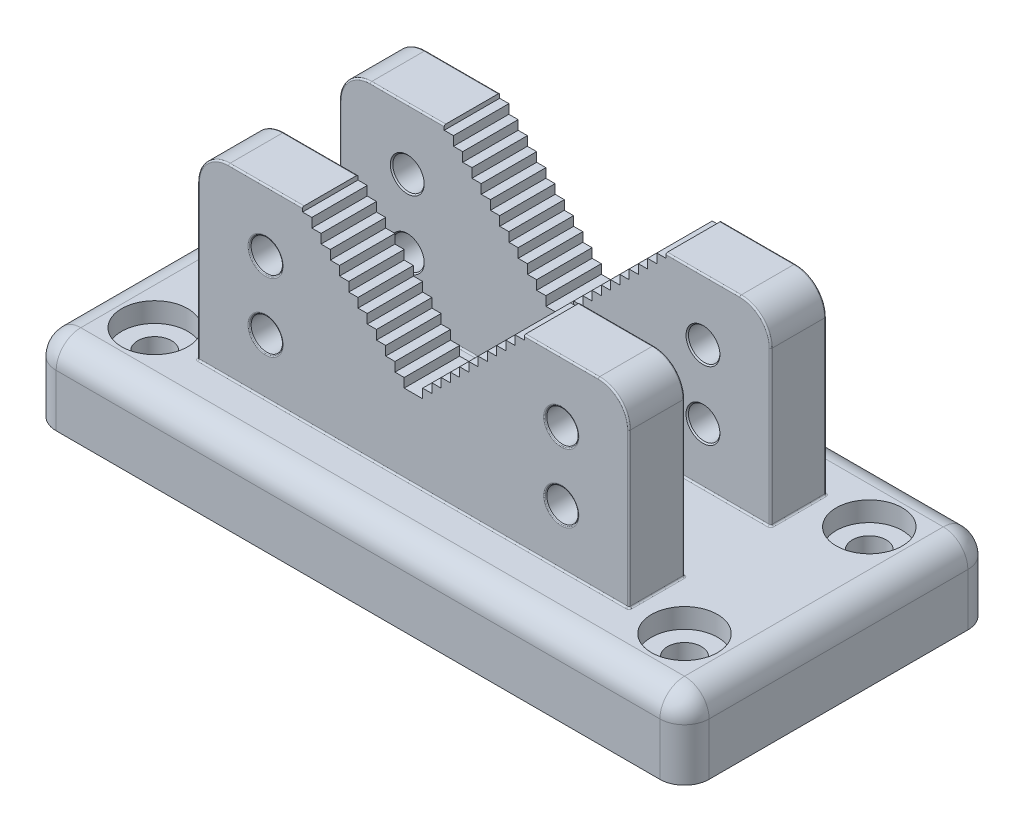
SolidWorks part; units mm, degrees
ref_plane "Front Plane" through (0, 0, 0) normal (0, 0, 1) x (1, 0, 0)
ref_plane "Top Plane" through (0, 0, 0) normal (0, 1, 0) x (1, 0, 0)
ref_plane "Right Plane" through (0, 0, 0) normal (1, 0, 0) x (0, 0, -1)
sketch "Sketch1" plane through (0, 0, 0) normal (0, 0, 1) x (1, 0, 0)
  line L0 (0, 0) -> (0, 51) construction
  line L1 (-106, 25) -> (106, 25)
  line L2 (-106, 25) -> (-106, 0)
  line L3 (-106, 0) -> (106, 0)
  line L4 (106, 25) -> (106, 0)
  line L5 (70, 25) -> (70, 75)
  line L6 (-70, 25) -> (-70, 75)
  line L7 (60, 85) -> (34, 85)
  line L8 (-60, 85) -> (-34, 85)
  line L9 (34, 85) -> (7.0711, 58.0711)
  line L10 (-34, 85) -> (-7.0711, 58.0711)
  arc A0 (70, 75) -> (60, 85) centre (60, 75) ccw
  arc A1 (-7.0711, 58.0711) -> (7.0711, 58.0711) centre (0, 65.1421) ccw
  arc A2 (-70, 75) -> (-60, 85) centre (-60, 75) cw
  circle A3 centre (48, 65.1421) radius 5
  circle A4 centre (-48, 65.1421) radius 5
  circle A5 centre (48, 43) radius 5
  circle A6 centre (-48, 43) radius 5
  point P16 (70, 85)
  point P22 (-70, 85)
  dimension "D7" = 10
  dimension "D8" = 10
  dimension "D1" = 25
  dimension "D2" = 212
  dimension "D3" = 51
  dimension "D4" = 60
  dimension "D5" = 90
  dimension "D6" = 36
  dimension "D9" = 48
  dimension "D10" = 18
extrude "Boss-Extrude1" add sketch "Sketch1" along normal mid plane 100 contours L3 L0 L1 L2 | L0 L3 L4 L1 region at (-53, 12.5, 0) region at (53, 12.5, 0)
extrude "Boss-Extrude2" add sketch "Sketch1<3>" along normal blind 18 from offset 14 contours A2 L6 L1 L5 A0 L7 L9 A1 L10 L8 A4 A3 A5 A6 region at (0, 51.7436, 0)
sketch "Sketch1<3>" plane through (0, 0, 0) normal (0, 0, 1) x (1, 0, 0) same geometry as "Sketch1"
extrude "Boss-Extrude3" add sketch "Sketch1<4>" against normal blind 18 from offset 14 contours A2 L6 L1 L5 A0 L7 L9 A1 L10 L8 A4 A3 A5 A6 region at (0, 51.7436, 0) offset against normal yes
sketch "Sketch1<4>" plane through (0, 0, 0) normal (0, 0, 1) x (1, 0, 0) same geometry as "Sketch1"
fillet "Fillet1" radius 8 4 edges at (-106, 25, 0) (0, 25, -50) (0, 25, 50) (106, 25, 0)
fillet "Fillet2" radius 8 4 edges at (103.6569, 22.6569, 47.6569) (103.6569, 22.6569, -47.6569) (106, 8.5, 50) (106, 8.5, -50)
fillet "Fillet3" radius 8 4 edges at (-103.6569, 22.6569, 47.6569) (-103.6569, 22.6569, -47.6569) (-106, 8.5, 50) (-106, 8.5, -50)
chamfer "Chamfer1" distance 0.5 angle 45 16 edges at (-43, 65.1421, 32) (-43, 65.1421, 14) (-43, 43, 14) (-43, 43, 32) (-43, 65.1421, -32) (-43, 43, -32) (-43, 43, -14) (-43, 65.1421, -14) (53, 65.1421, -14) (53, 43, -14) (53, 65.1421, -32) (53, 43, -32) (53, 43, 14) (53, 65.1421, 14) (53, 43, 32) (53, 65.1421, 32)
fillet "Fillet4" radius 0.5 57 edges at (0, 25, -14) (0, 25, 14) (-70, 25, -23) (70, 25, -23) (70, 25, 23) (-70, 25, 23) (70, 50, -14) (67.0711, 82.0711, -14) (20.5355, 71.5355, -14) (0, 55.1421, -14) (-70, 50, -14) (-67.0711, 82.0711, -14) (70, 50, 14) (67.0711, 82.0711, 14) (20.5355, 71.5355, 14) (0, 55.1421, 14) (-70, 50, 14) (-67.0711, 82.0711, 14) (-70, 50, -32) (0, 25, -32) (70, 50, -32) (67.0711, 82.0711, -32) (20.5355, 71.5355, -32) (0, 55.1421, -32) (-67.0711, 82.0711, -32) (53.5, 43, -32) (53.5, 65.1421, -32) (-42.5, 43, -32) (-42.5, 65.1421, -32) (0, 55.1421, 32) (20.5355, 71.5355, 32) (67.0711, 82.0711, 32) (70, 50, 32) (0, 25, 32) (-70, 50, 32) (-67.0711, 82.0711, 32) (53.5, 65.1421, 32) (53.5, 43, 32) (-42.5, 43, 32) (-42.5, 65.1421, 32) (34, 85, -23) (47, 85, -32) (47, 85, -14) (-20.5355, 71.5355, -32) (-20.5355, 71.5355, -14) (-47, 85, -32) (-34, 85, -23) (-47, 85, -14) (47, 85, 32) (34, 85, 23) (47, 85, 14) (-20.5355, 71.5355, 32) (-20.5355, 71.5355, 14) (-34, 85, 23) (-47, 85, 32) (-47, 85, 14) (-43, 43, -31.5)
sketch "Sketch2" plane through (0, 0, 32) normal (0, 0, 1) x (1, 0, 0)
  line L0 (-3, 50.5) -> (3, 50.5)
  line L1 (-6, 56.5) -> (-9, 56.5)
  line L2 (-69.5, 25.5) -> (69.5, 25.5) construction
  line L3 (-3, 50.5) -> (-3, 53.5)
  line L4 (-3, 53.5) -> (-6, 53.5)
  line L5 (-6, 53.5) -> (-6, 56.5)
  line L6 (-9, 59.5) -> (-12, 59.5)
  line L7 (-9, 56.5) -> (-9, 59.5)
  line L8 (-12, 62.5) -> (-15, 62.5)
  line L9 (-12, 59.5) -> (-12, 62.5)
  line L10 (-15, 65.5) -> (-18, 65.5)
  line L11 (-15, 62.5) -> (-15, 65.5)
  line L12 (-18, 68.5) -> (-21, 68.5)
  line L13 (-18, 65.5) -> (-18, 68.5)
  line L14 (-21, 71.5) -> (-24, 71.5)
  line L15 (-21, 68.5) -> (-21, 71.5)
  line L16 (-24, 74.5) -> (-27, 74.5)
  line L17 (-24, 71.5) -> (-24, 74.5)
  line L18 (-27, 77.5) -> (-30, 77.5)
  line L19 (-27, 74.5) -> (-27, 77.5)
  line L20 (-30, 80.5) -> (-33, 80.5)
  line L21 (-30, 77.5) -> (-30, 80.5)
  line L22 (-33, 83.5) -> (-36, 83.5)
  line L23 (-33, 80.5) -> (-33, 83.5)
  line L24 (-36, 86.5) -> (-39, 86.5)
  line L25 (-36, 83.5) -> (-36, 86.5)
  line L26 (0, -47.575) -> (0, 47.575) construction
  line L27 (36, 83.5) -> (36, 86.5)
  line L28 (36, 86.5) -> (39, 86.5)
  line L29 (33, 80.5) -> (33, 83.5)
  line L30 (33, 83.5) -> (36, 83.5)
  line L31 (30, 77.5) -> (30, 80.5)
  line L32 (30, 80.5) -> (33, 80.5)
  line L33 (27, 74.5) -> (27, 77.5)
  line L34 (27, 77.5) -> (30, 77.5)
  line L35 (24, 71.5) -> (24, 74.5)
  line L36 (24, 74.5) -> (27, 74.5)
  line L37 (21, 68.5) -> (21, 71.5)
  line L38 (21, 71.5) -> (24, 71.5)
  line L39 (18, 65.5) -> (18, 68.5)
  line L40 (18, 68.5) -> (21, 68.5)
  line L41 (15, 62.5) -> (15, 65.5)
  line L42 (15, 65.5) -> (18, 65.5)
  line L43 (12, 59.5) -> (12, 62.5)
  line L44 (12, 62.5) -> (15, 62.5)
  line L45 (9, 56.5) -> (9, 59.5)
  line L46 (9, 59.5) -> (12, 59.5)
  line L47 (6, 53.5) -> (6, 56.5)
  line L48 (3, 53.5) -> (6, 53.5)
  line L49 (3, 50.5) -> (3, 53.5)
  line L50 (6, 56.5) -> (9, 56.5)
  line L51 (-36, 86.5) -> (36, 86.5)
  point P2 (0, 50.5)
  line M30 (60, 84.5) -> (34.2071, 84.5)
  line M31 (34.2071, 84.5) -> (7.4246, 57.7175)
  arc M32 (7.4246, 57.7175) -> (-7.4246, 57.7175) centre (0, 65.1421) cw
  line M33 (-7.4246, 57.7175) -> (-34.2071, 84.5)
  line M34 (-34.2071, 84.5) -> (-60, 84.5)
  dimension "D1" = 6
  dimension "D2" = 25
  dimension "D3" = 3
  dimension "D4" = 12
extrude "Cut-Extrude4" cut sketch "Sketch2" against normal blind 70 contours L51 L25 L22 L23 L20 L21 L18 L19 L16 L17 L14 L15 L12 L13 L10 L11 L8 L9 L6 L7 L45 L46 L43 L44 L41 L42 L39 L40 L37 L38 L35 L36 M34 M33 M32 M31 | L25 L22 M33 M34 | L23 L20 M33 | L21 L18 M33 | L19 L16 M33 | L17 L14 M33 | L15 L12 M33 | L13 L10 M33 | L11 L8 M33 | L9 L6 M33 | L47 L50 L45 L7 L1 L5 L4 L3 L0 L49 L48 M31 M32 M33 | L46 L43 M31 | L44 L41 M31 | L42 L39 M31 | L40 L37 M31 | L38 L35 M31 | L36 L33 M31 | L34 L31 M31 | L32 L29 M31 | L30 L27 M31 M30 region at (0, 54.0197, 32) region at (0, 74.8399, 32) region at (-11.069, 60.431, 32) region at (11.069, 60.431, 32) region at (-14.069, 63.431, 32) region at (14.069, 63.431, 32) region at (-17.069, 66.431, 32) region at (17.069, 66.431, 32) region at (-20.069, 69.431, 32) region at (20.069, 69.431, 32) region at (-23.069, 72.431, 32) region at (23.069, 72.431, 32) region at (-26.069, 75.431, 32) region at (26.069, 75.431, 32) region at (-29.069, 78.431, 32) region at (29.069, 78.431, 32) region at (-32.069, 81.431, 32) region at (32.069, 81.431, 32) region at (-34.8354, 83.9637, 32) region at (34.8354, 83.9637, 32)
hole_wizard "CBORE for M10 Hex Head Bolt1" positions "Sketch3" profile "Sketch4" counterbore size "M10" standard "ISO" end condition through all
sketch "Sketch3" plane through (0, 25, 0) normal (0, 1, 0) x (1, 0, 0)
  line L0 (-98, 50) -> (98, 50) construction
  line L1 (106, 42) -> (106, -42) construction
  line L2 (98, -50) -> (-98, -50) construction
  line L3 (-106, -42) -> (-106, 42) construction
  point P0 (-86, 30)
  point P2 (86, 30)
  point P4 (86, -30)
  point P6 (-86, -30)
  point P15 (0, 0)
  point P16 (0, 0)
  dimension "D1" = 20
  dimension "D2" = 20
  dimension "D3" = 20
  dimension "D4" = 20
  dimension "D5" = 20
sketch "Sketch4" plane through (-86, 25, -30) normal (1, 0, 0) x (0, 0, 1)
  line L0 (0, 0) -> (0, 25)
  line L1 (0, 25) -> (5.5, 25)
  line L3 (5.5, 25) -> (5.5, 6.4)
  line L4 (5.5, 6.4) -> (10.7375, 6.4)
  line L5 (10.7375, 6.4) -> (10.7375, 0)
  line L7 (10.7375, 0) -> (0, 0)
  line L11 (0, -6.35) -> (0, 107.95) construction
  dimension "Thru Hole Dia." = 11
  dimension "Thru Hole Depth" = 25
  dimension "C'Bore Dia." = 21.475
  dimension "C'Bore Depth" = 6.4
hole_wizard "Ø10.2 (10.2) Diameter Hole1" positions "Sketch5" profile "Sketch6" hole size "Ø10.2" standard "ISO" end condition through all
sketch "Sketch5" plane through (0, 0, 32) normal (0, 0, 1) x (1, 0, 0)
  point P0 (48, 65.1421)
  point P3 (-48, 65.1421)
  point P6 (-48, 43)
  point P9 (48, 43)
sketch "Sketch6" plane through (48, 65.1421, 32) normal (1, 0, 0) x (0, -1, 0)
  line L0 (0, 0) -> (0, 82)
  line L1 (0, 82) -> (5.1, 82)
  line L2 (5.1, 82) -> (5.1, 0)
  line L5 (5.1, 0) -> (0, 0)
  line L11 (0, -6.35) -> (0, 107.95) construction
  dimension "Thru Hole Dia." = 10.2
  dimension "Thru Hole Depth" = 82
